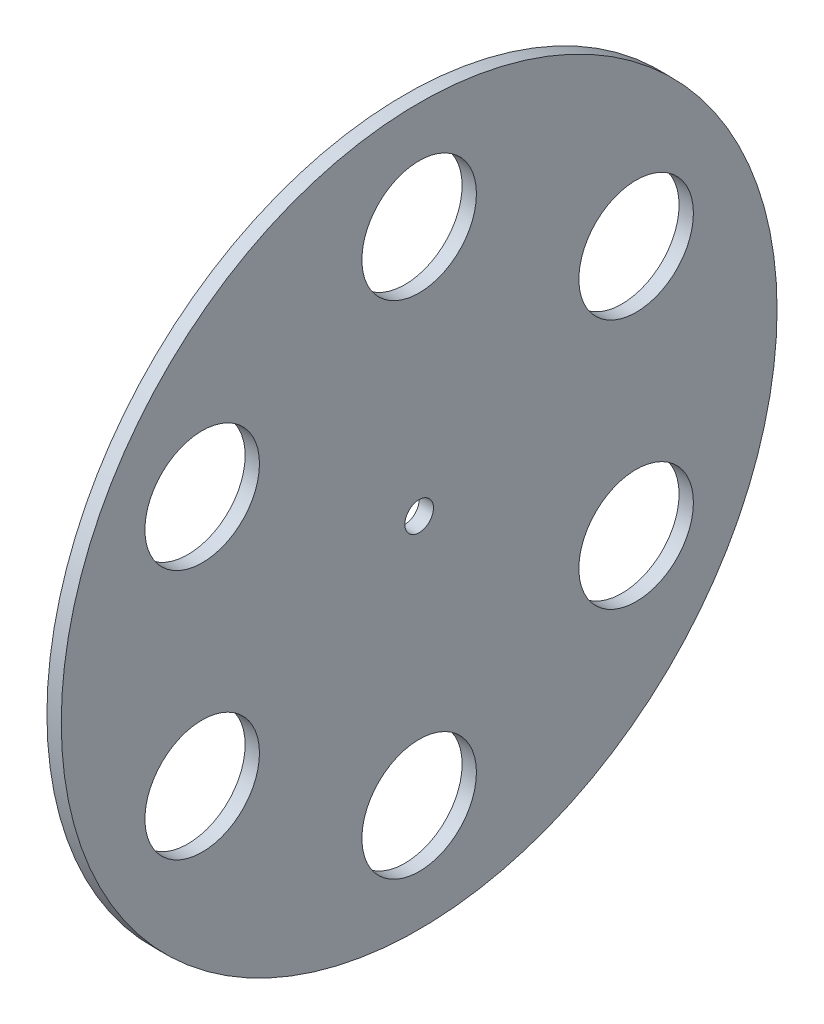
SolidWorks part; units mm, degrees
material "AISI 304"
ref_plane "Front Plane" through (0, 0, 0) normal (0, 0, 1) x (1, 0, 0)
ref_plane "Top Plane" through (0, 0, 0) normal (0, 1, 0) x (1, 0, 0)
ref_plane "Right Plane" through (0, 0, 0) normal (1, 0, 0) x (0, 0, -1)
sketch "Sketch1" plane through (0, 0, 0) normal (1, 0, 0) x (0, 0, -1)
  line L0 (0, 0) -> (0, 250) construction
  line L1 (0, 0) -> (216.5064, 125) construction
  line L2 (0, 0) -> (216.5064, -125) construction
  line L3 (0, 0) -> (0, -250) construction
  line L4 (0, 0) -> (-216.5064, -125) construction
  line L5 (0, 0) -> (-216.5064, 125) construction
  circle A0 centre (0, 0) radius 250
  circle A1 centre (0, 0) radius 10
  circle A2 centre (0, 175) radius 40
  circle A3 centre (151.5544, 87.5) radius 40
  circle A4 centre (151.5544, -87.5) radius 40
  circle A5 centre (0, -175) radius 40
  circle A6 centre (-151.5544, -87.5) radius 40
  circle A7 centre (-151.5544, 87.5) radius 40
  point P13 (0, 0)
  point P26 (0, 0)
  dimension "D1" = 500
  dimension "D2" = 20
  dimension "D4" = 80
  dimension "D5" = 175
  dimension "D3" = 6
  dimension "D6" = 6
extrude "Boss-Extrude1" add sketch "Sketch1" along normal blind 10
ref_plane "Plane1" through (10, 0, 0) normal (-1, 0, 0) x (0, 0, 1)
